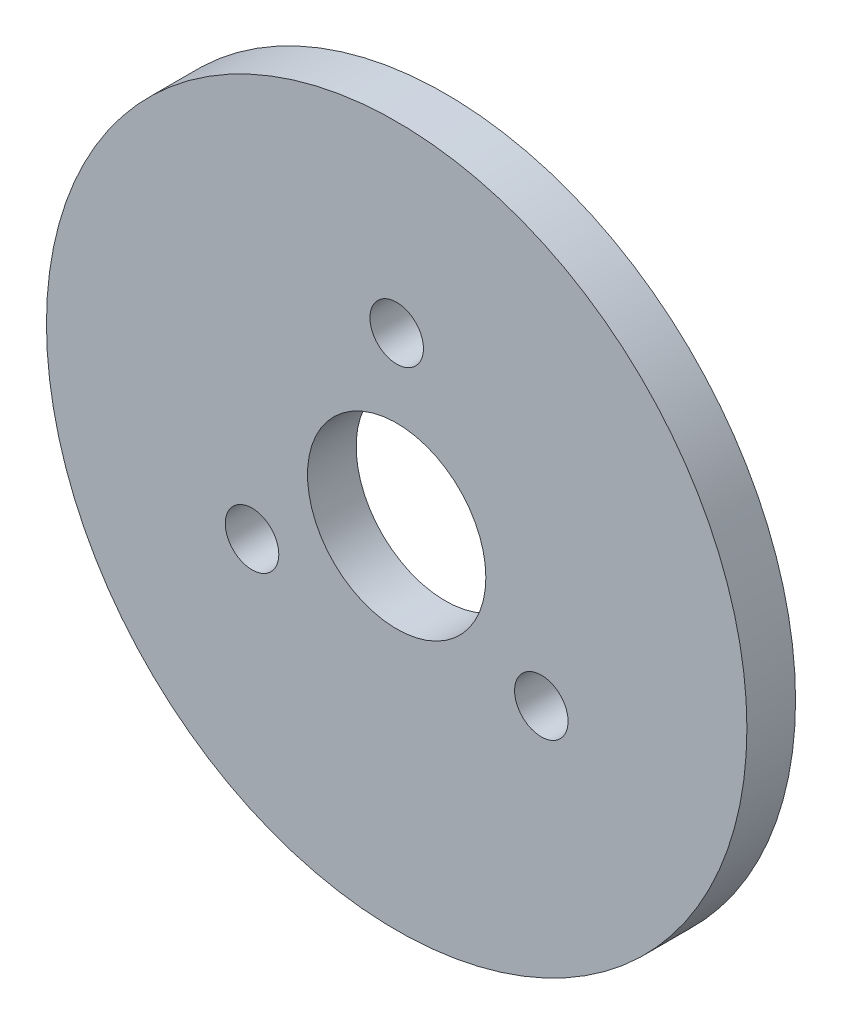
SolidWorks part; units mm, degrees
ref_plane "Front Plane" through (0, 0, 0) normal (0, 0, 1) x (1, 0, 0)
ref_plane "Top Plane" through (0, 0, 0) normal (0, 1, 0) x (1, 0, 0)
ref_plane "Right Plane" through (0, 0, 0) normal (1, 0, 0) x (0, 0, -1)
sketch "Sketch1" plane through (0, 0, 0) normal (0, 0, 1) x (1, 0, 0)
  circle A0 centre (0, 0) radius 21.6
  circle A1 centre (0, 0) radius 5.5
  dimension "D1" = 43.2
  dimension "D2" = 11
extrude "Boss-Extrude1" add sketch "Sketch1" along normal blind 3
sketch "Sketch2" plane through (0, 0, 3) normal (0, 0, 1) x (1, 0, 0)
  line L0 (0, 0) -> (0, 50000) construction
  line L1 (0, 0) -> (50000, 0) construction
  circle A0 centre (0, 10.3) radius 1.65
  circle A1 centre (0, 0) radius 5.5 construction
  circle A2 centre (8.9201, -5.15) radius 1.65
  circle A3 centre (-8.9201, -5.15) radius 1.65
  point P16 (0, 0)
  dimension "D1" = 3.3
  dimension "D2" = 10.3
  dimension "D3" = 3
extrude "Cut-Extrude1" cut sketch "Sketch2" against normal blind 3
